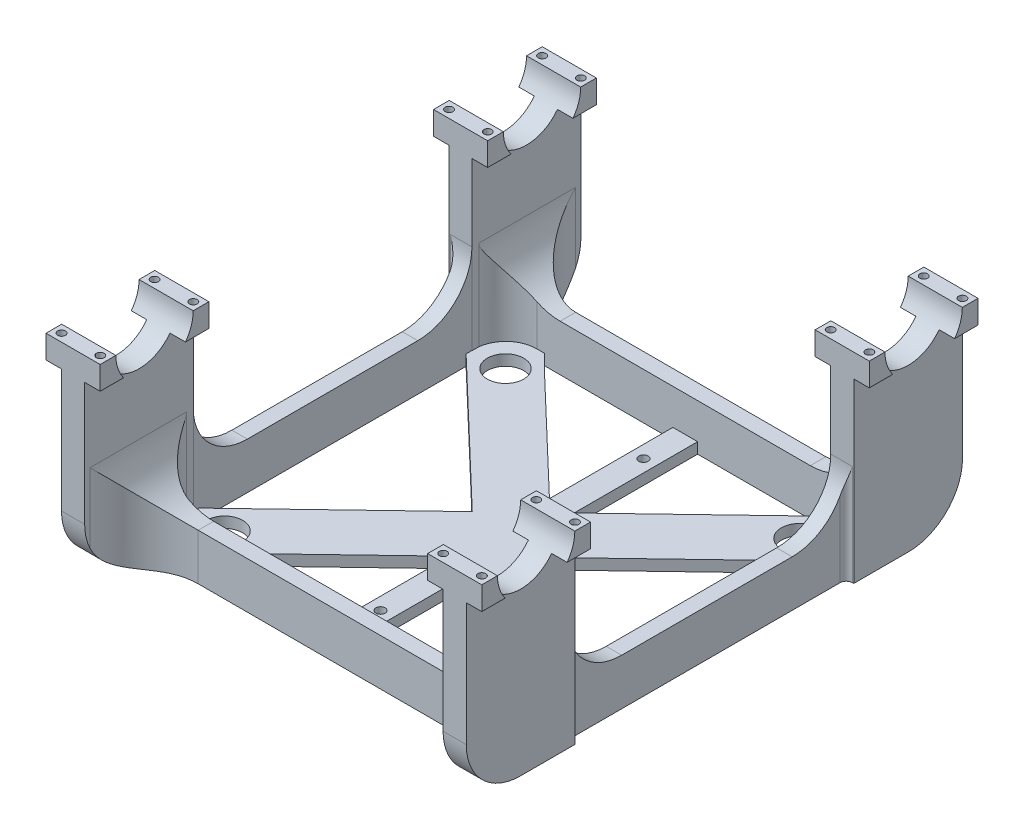
SolidWorks part; units mm, degrees
ref_plane "Front Plane" through (0, 0, 0) normal (0, 0, 1) x (1, 0, 0)
ref_plane "Top Plane" through (0, 0, 0) normal (0, 1, 0) x (1, 0, 0)
ref_plane "Right Plane" through (0, 0, 0) normal (1, 0, 0) x (0, 0, -1)
sketch "Sketch1" plane through (0, 0, 0) normal (0, 1, 0) x (1, 0, 0)
  line L0 (-58, -56) -> (58, -56)
  line L1 (-58, -56) -> (-58, 56)
  line L2 (58, -56) -> (58, 56)
  line L3 (-58, 56) -> (58, 56)
  line L4 (-58, -56) -> (58, 56) construction
  line L5 (58, -56) -> (-58, 56) construction
  line L6 (-63, -61) -> (-63, 61)
  line L7 (-63, 61) -> (63, 61)
  line L8 (63, -61) -> (63, 61)
  line L9 (-63, -61) -> (63, -61)
  point P1 (0, 0)
  dimension "D1" = 116
  dimension "D2" = 112
  dimension "D3" = 5
extrude "Boss-Extrude1" add sketch "Sketch1" along normal blind 15
fillet "Fillet1" radius 10 1 edges at (58, 7.5, -56)
fillet "Fillet2" radius 10 1 edges at (-58, 7.5, -56)
fillet "Fillet3" radius 10 1 edges at (-58, 7.5, 56)
fillet "Fillet4" radius 10 1 edges at (58, 7.5, 56)
sketch "Sketch4" plane through (0, 15, 0) normal (0, 1, 0) x (1, 0, 0)
  line L0 (-63, 61) -> (-63, 62.625)
  line L1 (-63, 62.625) -> (-61.675, 62.625)
  line L2 (-61.675, 62.625) -> (-61.675, 80.1975)
  line L3 (-61.675, 80.1975) -> (-57.925, 80.1975)
  line L4 (-65.425, 45.0525) -> (-65.425, 80.1975)
  line L5 (-65.425, 45.0525) -> (-57.925, 45.0525)
  line L6 (-65.425, 80.1975) -> (-57.925, 80.1975)
  line L7 (-57.925, 45.0525) -> (-57.925, 80.1975)
  line L8 (-65.425, 45.0525) -> (-57.925, 80.1975) construction
  line L9 (-65.425, 80.1975) -> (-57.925, 45.0525) construction
  dimension "D1" = 1.625
  dimension "D2" = 1.325
  dimension "D3" = 3.75
extrude "Boss-Extrude3" add sketch "Sketch4" along normal blind 49.75 and the other way up to surface contours L6 L4 L5 L7
sketch "Sketch5" plane through (-57.925, 0, 0) normal (1, 0, 0) x (0, 0, -1)
  line L0 (45.0525, 64.75) -> (80.1975, 64.75) construction
  circle A0 centre (62.625, 64.75) radius 12.5
  dimension "D1" = 25
extrude "Cut-Extrude1" cut sketch "Sketch5" against normal through all
ref_plane "Plane1" through (-61.675, 0, 0) normal (1, 0, 0) x (0, 0, -1)
sketch "Sketch6" plane through (-57.925, 0, 0) normal (1, 0, 0) x (0, 0, -1)
  line L0 (45.0525, 64.75) -> (50.125, 64.75)
  line L1 (45.0525, 64.75) -> (45.0525, 57.25)
  line L2 (45.0525, 0) -> (45.0525, 64.75) construction
  line L3 (45.0525, 57.25) -> (52.625, 57.25)
  arc A0 (50.125, 64.75) -> (75.125, 64.75) centre (62.625, 64.75) ccw construction
  arc A1 (52.625, 57.25) -> (50.125, 64.75) centre (62.625, 64.75) cw
  dimension "D1" = 7.5
extrude "Boss-Extrude4" add sketch "Sketch6" along normal blind 5
sketch "Sketch9" plane through (0, 64.75, 0) normal (0, 1, 0) x (1, 0, 0)
  line L0 (-52.925, 47.5887) -> (-55.425, 47.5887)
  line L1 (-52.925, 50.125) -> (-52.925, 45.0525) construction
  circle A0 centre (-55.425, 47.5887) radius 1.25
  dimension "D2" = 2.5
  dimension "D1" = 2.5
extrude "Cut-Extrude3" cut sketch "Sketch9" against normal through all
mirror "Mirror1" about plane through (-61.675, 0, 0) normal (1, 0, 0) of "Cut-Extrude3", "Boss-Extrude4"
ref_plane "Plane2" through (0, 0, -62.625) normal (0, 0, -1) x (-1, 0, 0)
mirror "Mirror2" about plane through (0, 0, -62.625) normal (0, 0, -1) of "Mirror1", "Boss-Extrude4", "Cut-Extrude3"
fillet "Fillet6" radius 17.5 1 edges at (-57.925, 7.5, -61)
fillet "Fillet7" radius 17.5 3 edges at (-52.7994, 15, -66.1256) (-54.6248, 15, -53.4908) (-57.925, 15, -62.8612)
fillet "Fillet8" radius 2 1 edges at (-63, 7.5, -45.0525)
fillet "Fillet9" radius 17.5 2 edges at (-63.5858, 15, -44.4667) (-61.5, 15, -45.0525)
fillet "Fillet10" radius 17.5 2 edges at (-57.925, 0, -79.3488) (-61.675, 0, -80.1975)
mirror "Mirror4" about plane through (0, 0, 0) normal (0, 0, 1) of "Mirror2", "Mirror1", "Cut-Extrude3", "Boss-Extrude4", "Cut-Extrude1", "Boss-Extrude3"
fillet "Fillet11" radius 2 1 edges at (-63, 7.5, 45.0525)
fillet "Fillet12" radius 17.5 2 edges at (-61.5, 15, 45.0525) (-63.5858, 15, 44.4667)
fillet "Fillet13" radius 17.5 1 edges at (-57.925, 7.5, 61)
fillet "Fillet14" radius 17.5 3 edges at (-54.6248, 15, 53.4908) (-57.925, 15, 62.8612) (-52.7994, 15, 66.1256)
fillet "Fillet15" radius 17.5 2 edges at (-57.925, 0, 79.3488) (-61.675, 0, 80.1975)
mirror "Mirror6" about plane through (0, 0, 0) normal (1, 0, 0) of "Mirror4", "Boss-Extrude3", "Cut-Extrude1", "Boss-Extrude4", "Cut-Extrude3", "Mirror1", "Mirror2"
fillet "Fillet16" radius 2 1 edges at (63, 7.5, 45.0525)
fillet "Fillet17" radius 17.5 2 edges at (61.5, 15, 45.0525) (63.5858, 15, 44.4667)
fillet "Fillet18" radius 2 1 edges at (63, 7.5, -45.0525)
fillet "Fillet19" radius 17.5 2 edges at (61.5, 15, -45.0525) (63.5858, 15, -44.4667)
fillet "Fillet20" radius 17.5 1 edges at (57.925, 7.5, -61)
fillet "Fillet21" radius 17.5 3 edges at (54.6248, 15, -53.4908) (57.925, 15, -62.8612) (52.7994, 15, -66.1256)
fillet "Fillet22" radius 17.5 1 edges at (57.925, 7.5, 61)
fillet "Fillet23" radius 17.5 3 edges at (57.925, 15, 62.8612) (54.6248, 15, 53.4908) (52.7994, 15, 66.1256)
fillet "Fillet24" radius 17.5 2 edges at (57.925, 0, 79.3488) (61.675, 0, 80.1975)
fillet "Fillet25" radius 17.5 2 edges at (57.925, 0, -79.3488) (61.675, 0, -80.1975)
sketch "Sketch11" plane through (0, 0, 0) normal (0, -1, 0) x (-1, 0, 0)
  line L0 (0, 0) -> (0, 45.4)
  line L1 (0, 45.4) -> (-47.5, 45.4)
  line L3 (-8.25, 0) -> (8.25, 0) construction
  line L4 (0, 8.25) -> (0, -8.25) construction
  line L5 (-47.5, 45.4) -> (47.5, -45.4)
  line L6 (47.5, -45.4) -> (41.3679, -51.8158)
  line L7 (41.3679, -51.8158) -> (-58, 43.159)
  line L8 (-58, -45.0525) -> (-58, 45.0525) construction
  line L9 (41.3679, -51.8158) -> (45.5521, -56)
  line L10 (48, -56) -> (-48, -56) construction
  line L11 (47.5, -45.4) -> (53.7756, -39.1244)
  line L12 (-47.5, 45.4) -> (-41.2244, 51.6756)
  line L13 (-41.2244, 51.6756) -> (53.7756, -39.1244)
  line L14 (53.7756, -39.1244) -> (58, -43.1622)
  line L15 (58, 45.0525) -> (58, -45.0525) construction
  line L16 (-41.2244, 51.6756) -> (-45.7489, 56)
  line L17 (-48, 56) -> (48, 56) construction
  circle A0 centre (-47.5, 45.4) radius 5.875
  circle A1 centre (-47.5, 45.4) radius 8.875
  circle A4 centre (-47.5, -45.4) radius 8.875
  circle A5 centre (-47.5, -45.4) radius 5.875
  circle A6 centre (47.5, 45.4) radius 8.875
  circle A7 centre (47.5, 45.4) radius 5.875
  circle A8 centre (47.5, -45.4) radius 8.875
  circle A9 centre (47.5, -45.4) radius 5.875
  arc A10 (-58, 43.159) -> (-45.7489, 56) centre (-47.5646, 45.4677) cw
  arc A11 (45.5521, -56) -> (58, -43.1622) centre (48.4327, -46.3393) ccw
  line M27 (-58, -45.0525) -> (-58, 45.0525)
  line M28 (-58, 45.0525) -> (-57.925, 45.0525)
  line M29 (-57.925, 45.0525) -> (-57.925, 47.2224)
  arc M30 (-57.925, 47.2224) -> (-48, 56) centre (-48, 46) cw
  line M31 (-48, 56) -> (48, 56)
  line M35 (58, 45.0525) -> (58, -45.0525)
  line M36 (58, -45.0525) -> (57.925, -45.0525)
  line M37 (57.925, -45.0525) -> (57.925, -47.2224)
  arc M38 (57.925, -47.2224) -> (48, -56) centre (48, -46) cw
  line M39 (48, -56) -> (-48, -56)
  dimension "D3" = 11.75
  dimension "D4" = 17.75
  dimension "D1" = 45.4
  dimension "D2" = 47.5
extrude "Boss-Extrude5" add sketch "Sketch11" against normal blind 3.5 contours A8 L9 L14 M39 M38 M37 M36 M35 | A9 L6 A8 L11 | A9 L5 A8 L6 | A9 L11 L13 A8 L5 | A8 L5 A1 L7 | A8 L13 L0 L5 | A1 L5 L0 L13 L1 | A1 L1 L13 | L5 A1 L1 A0 | L1 A1 L12 A0 | A1 L5 A0 L12 L16 | A1 L16 L7 M31 M30 M29 M28 M27
mirror "Mirror7" about plane through (0, 0, 0) normal (0, 0, 1) of "Boss-Extrude5"
sketch "Sketch12" plane through (0, 0, 0) normal (0, -1, 0) x (-1, 0, 0)
  line L0 (0, 0) -> (-4, 0)
  line L1 (0, 0) -> (-0.0984, 56)
  line L2 (-45.7489, 56) -> (45.5521, 56) construction
  line L3 (4, -56.5079) -> (-4, -56.5079)
  line L4 (4, -56.5079) -> (4, 56.5079)
  line L5 (-4, -56.5079) -> (-4, 56.5079)
  line L6 (4, 56.5079) -> (-4, 56.5079)
  line L7 (4, -56.5079) -> (-4, 56.5079) construction
  line L8 (-4, -56.5079) -> (4, 56.5079) construction
  line M6 (-45.7489, -56) -> (-0.0016, -12.2753)
  line M7 (-0.0016, -12.2753) -> (41.3679, -51.8158)
  line M9 (45.5521, -56) -> (-45.7489, -56)
  line M13 (41.3679, 51.8158) -> (-0.0016, 12.2753)
  line M14 (-0.0016, 12.2753) -> (-45.7489, 56)
  line M15 (-45.7489, 56) -> (45.5521, 56)
  dimension "D1" = 4
extrude "Boss-Extrude6" add sketch "Sketch12" against normal up to surface (3.5 mm away) contours L4 L1 M13 M15 M14 | L5 L1 M14 M15 | L5 L4 M9 M7 M6 up to face at (47.5, 3.5, -51.275)
sketch "Sketch13" plane through (0, 0, 0) normal (0, -1, 0) x (-1, 0, 0)
  line L0 (0, 0) -> (0, 42.5)
  circle A0 centre (0, 42.5) radius 1.5
  dimension "D2" = 3
  dimension "D1" = 42.5
extrude "Cut-Extrude4" cut sketch "Sketch13" against normal through all
mirror "Mirror8" about plane through (0, 0, 0) normal (0, 0, 1) of "Cut-Extrude4"
